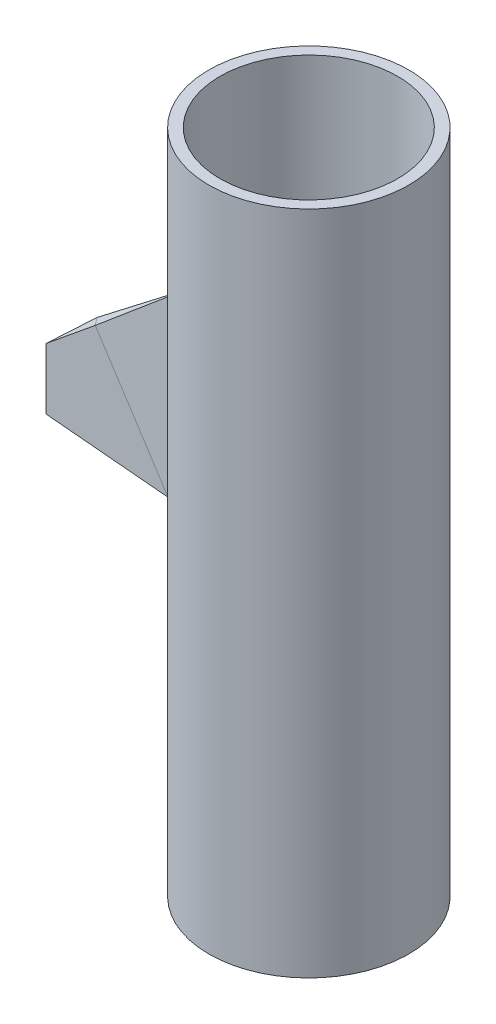
SolidWorks part; units mm, degrees
ref_plane "Front Plane" through (0, 0, 0) normal (0, 0, 1) x (1, 0, 0)
ref_plane "Top Plane" through (0, 0, 0) normal (0, 1, 0) x (1, 0, 0)
ref_plane "Right Plane" through (0, 0, 0) normal (1, 0, 0) x (0, 0, -1)
sketch "Sketch5" plane through (0, 0, 0) normal (0, 1, 0) x (1, 0, 0)
  circle A0 centre (0, 0) radius 40
  circle A1 centre (0, 0) radius 45
  dimension "D1" = 5
extrude "Boss-Extrude6" add sketch "Sketch5" along normal blind 300
sketch "Sketch6" plane through (0, 0, 0) normal (0, 0, 1) x (1, 0, 0)
  line L0 (-58.3899, 209.0102) -> (-58.3899, 129.0102)
  line L1 (-58.3899, 129.0102) -> (-118.3899, 129.0102)
  line L2 (-118.3899, 129.0102) -> (-118.3899, 159.0102)
  line L3 (-118.3899, 159.0102) -> (-58.3899, 209.0102)
extrude "Boss-Extrude7" add sketch "Sketch6" along normal mid plane 10 separate body
sketch "Sketch7" plane through (-58.3899, 0, 0) normal (1, 0, 0) x (0, 0, -1)
  line L0 (-5, 129.0102) -> (0, 209.0102)
  line L1 (-5, 209.0102) -> (5, 209.0102) construction
  line L2 (0, 209.0102) -> (5, 129.0102)
  line L3 (5, 129.0102) -> (-5, 129.0102)
extrude "Cut-Extrude2" cut sketch "Sketch7" against normal up to next (60 mm away) flip side to cut
sketch "Sketch8" plane through (0, 129.0102, 0) normal (0, -1, 0) x (1, 0, 0)
  line L0 (-58.3899, 5) -> (-118.3899, 0)
  line L1 (-118.3899, 5) -> (-118.3899, -5) construction
  line L2 (-118.3899, 0) -> (-58.3899, -5)
  line L3 (-58.3899, -5) -> (-58.3899, 5)
extrude "Cut-Extrude4" cut sketch "Sketch8" against normal up to next (63.3333 mm away) flip side to cut
fillet "Chamfer1" radius 2 4 edges at (-76.8514, 193.6256, -0.9615) (-76.8514, 193.6256, 0.9615) (-106.8514, 168.6256, 0.9615) (-106.8514, 168.6256, -0.9615) profile chamfer
sketch "Sketch9" plane through (-58.3899, 0, 0) normal (1, 0, 0) x (0, 0, -1)
  circle A0 centre (0, 162.2293) radius 2
extrude "Cut-Extrude5" cut sketch "Sketch9" against normal blind 10
